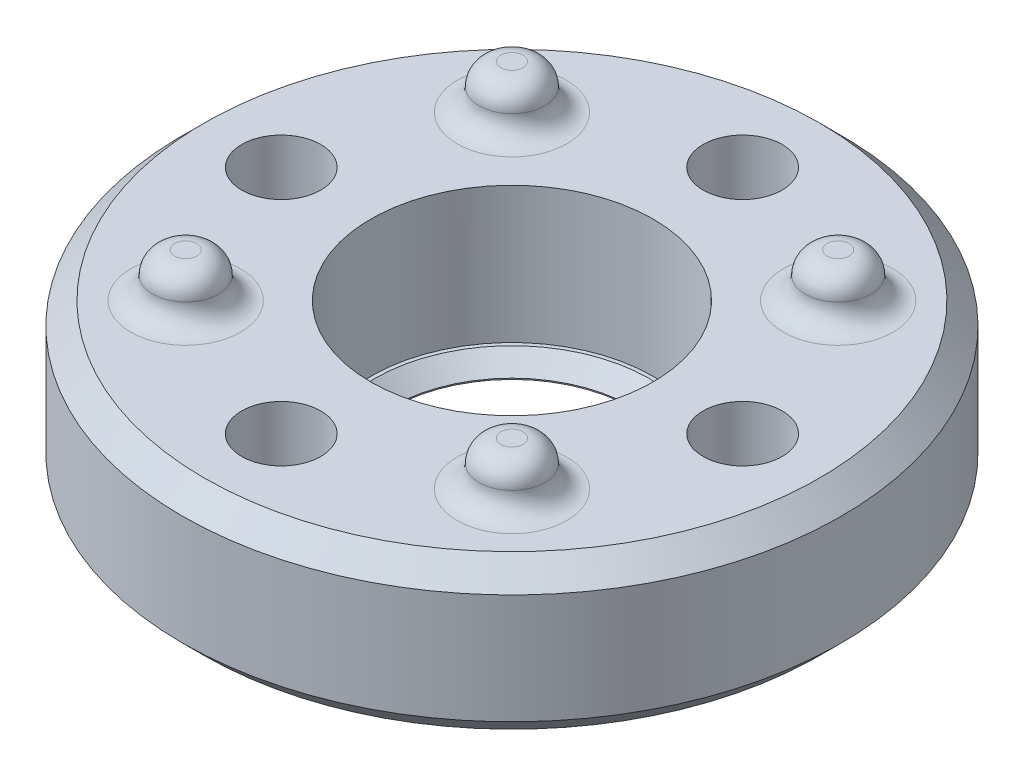
SolidWorks part; units mm, degrees
ref_plane "Front Plane" through (0, 0, 0) normal (0, 0, 1) x (1, 0, 0)
ref_plane "Top Plane" through (0, 0, 0) normal (0, 1, 0) x (1, 0, 0)
ref_plane "Right Plane" through (0, 0, 0) normal (1, 0, 0) x (0, 0, -1)
sketch "Sketch1" plane through (0, 0, 0) normal (0, 1, 0) x (1, 0, 0)
  circle A0 centre (0, 0) radius 15
  circle A1 centre (0, 0) radius 6.425
  dimension "D1" = 12.85
  dimension "D2" = 30
extrude "Boss-Extrude1" add sketch "Sketch1" along normal blind 7
sketch "Sketch2" plane through (0, 0, 0) normal (0, -1, 0) x (1, 0, 0)
  circle A0 centre (0, 0) radius 10.5 construction
  circle A1 centre (0, 10.5) radius 1.8
  circle A2 centre (10.5, 0) radius 1.8
  circle A3 centre (0, -10.5) radius 1.8
  circle A4 centre (-10.5, 0) radius 1.8
  point P14 (0, 0)
  dimension "D1" = 21
  dimension "D2" = 3.6
  dimension "D3" = 4
extrude "Cut-Extrude1" cut sketch "Sketch2" against normal through all
sketch "Sketch3" plane through (0, 0, 0) normal (0, -1, 0) x (1, 0, 0)
  circle A0 centre (0, 10.5) radius 3.25
  circle A1 centre (10.5, 0) radius 3.25
  circle A2 centre (0, -10.5) radius 3.25
  circle A3 centre (-10.5, 0) radius 3.25
  point P12 (0, 0)
  dimension "D2" = 6.5
  dimension "D1" = 4
extrude "Cut-Extrude2" cut sketch "Sketch3" against normal blind 2
fillet "Fillet1" radius 1.5 4 edges at (-10.5, 2, -3.25) (0, 2, -13.75) (10.5, 2, -3.25) (0, 2, 7.25)
chamfer "Chamfer1" distance 1 angle 45 1 edges at (0, 7, 15)
chamfer "Chamfer2" distance 1 angle 45 1 edges at (0, 0, 15)
sketch "Sketch4" plane through (0, 7, 0) normal (0, 1, 0) x (1, 0, 0)
  line L0 (0, 0) -> (10.5, 0) construction
  line L1 (0, 0) -> (0, 10.5) construction
  arc A0 (0, 10.5) -> (10.5, 0) centre (0, 0) cw construction
  circle A1 centre (7.4246, 7.4246) radius 1.5
  circle A2 centre (7.4246, -7.4246) radius 1.5
  circle A3 centre (-7.4246, -7.4246) radius 1.5
  circle A4 centre (-7.4246, 7.4246) radius 1.5
  point P9 (0, 0)
  point P18 (0, 0)
  dimension "D1" = 3
  dimension "D2" = 4
extrude "Boss-Extrude2" add sketch "Sketch4" along normal blind 2
fillet "Fillet2" radius 1 8 edges at (7.4246, 9, 8.9246) (7.4246, 9, -5.9246) (-7.4246, 9, 8.9246) (-7.4246, 9, -5.9246) (-7.4246, 7, -5.9246) (-7.4246, 7, 8.9246) (7.4246, 7, -5.9246) (7.4246, 7, 8.9246)
sketch "Sketch5" plane through (0, 0, 0) normal (0, -1, 0) x (1, 0, 0)
  circle A0 centre (0, 0) radius 6.6799
  circle A1 centre (0, 0) radius 5.5
  dimension "D1" = 11
extrude "Boss-Extrude3" add sketch "Sketch5" against normal blind 0.8
chamfer "Chamfer3" distance 0.75 angle 45 1 edges at (0, 0.8, -5.5)
